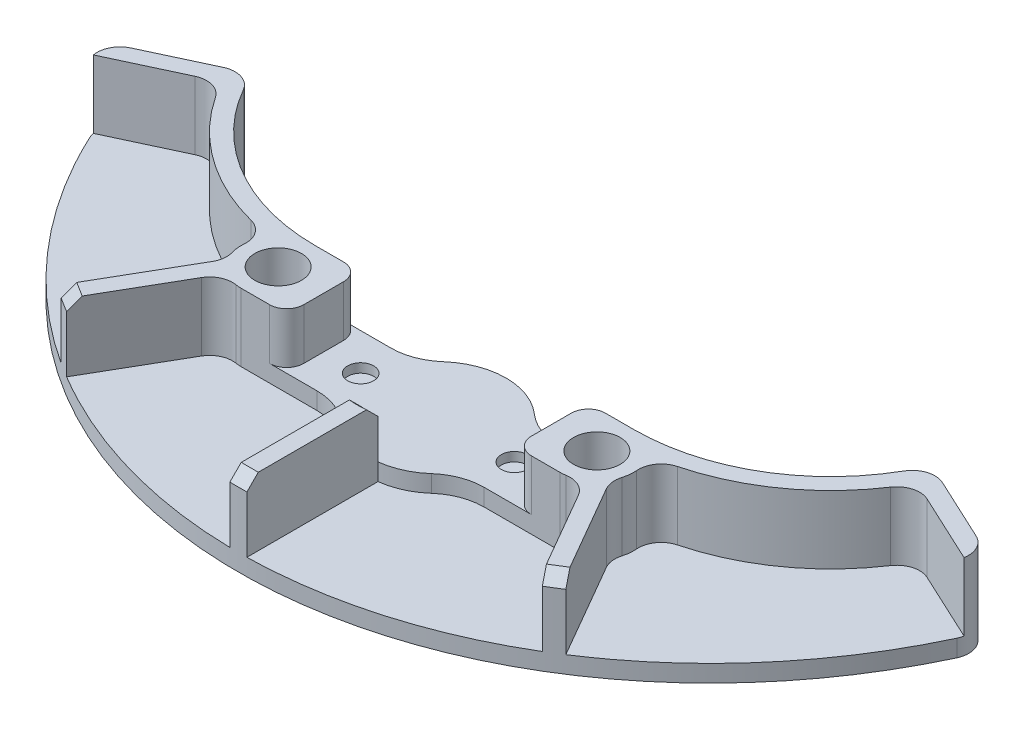
SolidWorks part; units mm, degrees
material "Custom Plastic"
ref_plane "Front Plane" through (0, 0, 0) normal (0, 0, 1) x (1, 0, 0)
ref_plane "Top Plane" through (0, 0, 0) normal (0, 1, 0) x (1, 0, 0)
ref_plane "Right Plane" through (0, 0, 0) normal (1, 0, 0) x (0, 0, -1)
sketch "Sketch1" plane through (0, 0, 0) normal (0, 1, 0) x (1, 0, 0)
  line L0 (-1000, 0) -> (49000, 0) construction
  line L1 (0, -1000) -> (0, 49000) construction
  line L2 (-7.3514, 3.25) -> (-14, 3.25)
  line L3 (-7.3514, -3.25) -> (-14, -3.25)
  line L4 (7.3514, -3.25) -> (14, -3.25)
  line L5 (7.3514, 3.25) -> (14, 3.25)
  circle A1 centre (-6.75, 0) radius 1.14
  arc A5 (3.99, 4.5211) -> (-3.99, 4.5211) centre (0, 0) ccw
  arc A6 (-7.3514, 3.25) -> (-3.99, 4.5211) centre (-7.3514, 8.33) ccw
  circle A17 centre (-14, 0) radius 2.05
  arc A18 (-14, 3.25) -> (-14, -3.25) centre (-14, 0) ccw
  arc A19 (3.99, -4.5211) -> (-3.99, -4.5211) centre (0, 0) cw
  arc A20 (-7.3514, -3.25) -> (-3.99, -4.5211) centre (-7.3514, -8.33) cw
  arc A21 (7.3514, 3.25) -> (3.99, 4.5211) centre (7.3514, 8.33) cw
  arc A22 (7.3514, -3.25) -> (3.99, -4.5211) centre (7.3514, -8.33) ccw
  circle A23 centre (6.75, 0) radius 1.14
  circle A24 centre (14, 0) radius 2.05
  arc A25 (14, 3.25) -> (14, -3.25) centre (14, 0) cw
  dimension "D1" = 6.03
  dimension "D3" = 2.28
  dimension "D4" = 5.08
  dimension "D6" = 4.1
  dimension "D8" = 6.5
  dimension "D2" = 13.5
  dimension "D7" = 28
extrude "Boss-Extrude2" add sketch "Sketch1" along normal blind 1.5
sketch "Sketch2" plane through (0, 1.5, 0) normal (0, 1, 0) x (1, 0, 0)
  line L0 (0, -1000) -> (0, 49000) construction
  line L1 (-14, 3.25) -> (-10, 3.25)
  line L2 (-7.3514, 3.25) -> (-14, 3.25) construction
  line L3 (-10, 3.25) -> (-10, -3.25)
  line L4 (-14, -3.25) -> (-7.3514, -3.25) construction
  line L5 (-10, -3.25) -> (-14, -3.25)
  line L6 (10, -3.25) -> (14, -3.25)
  line L7 (10, 3.25) -> (10, -3.25)
  line L8 (14, 3.25) -> (10, 3.25)
  arc A0 (-14, 3.25) -> (-14, -3.25) centre (-14, 0) ccw
  circle A2 centre (-14, 0) radius 2.05 construction
  circle A3 centre (-14, 0) radius 2.05
  circle A4 centre (14, 0) radius 2.05
  arc A5 (14, 3.25) -> (14, -3.25) centre (14, 0) cw
  dimension "D1" = 4
extrude "Boss-Extrude3" add sketch "Sketch2" along normal blind 4.47
fillet "Fillet1" radius 1.5 4 edges at (10, 3.735, 3.25) (10, 3.735, -3.25) (-10, 3.735, 3.25) (-10, 3.735, -3.25)
sketch "Sketch3" plane through (0, 0, 0) normal (0, -1, 0) x (1, 0, 0)
  line L0 (0, -1000) -> (0, 49000) construction
  line L1 (-1000, -27.5) -> (49000, -27.5) construction
  line L2 (0, -27.5) -> (-45315.3894, 21103.4131) construction
  line L3 (0, -27.5) -> (-16.815, 1.6244) construction
  line L4 (0, -27.5) -> (45315.3894, 21103.4131) construction
  line L5 (0, -27.5) -> (16.815, 1.6244) construction
  line L6 (-38.8951, -9.3629) -> (-29.832, -13.5891)
  line L7 (-22.1669, 10.8942) -> (-17.3063, 2.4755)
  line L8 (22.1669, 10.8942) -> (17.3063, 2.4755)
  line L9 (38.8951, -9.3629) -> (29.832, -13.5891)
  line L10 (14, -3.25) -> (7.3514, -3.25) construction
  line L11 (-7.3514, -3.25) -> (-14, -3.25) construction
  line L12 (14, -3.25) -> (7.3514, -3.25)
  line L13 (-7.3514, -3.25) -> (-14, -3.25)
  line L14 (17.3063, 2.4755) -> (25000, 43273.7702) construction
  line L15 (-17.3063, 2.4755) -> (-25000, 43273.7702) construction
  arc A0 (-14, 3.25) -> (-14, -3.25) centre (-14, 0) ccw construction
  arc A1 (-16.815, 1.6244) -> (-14, -3.25) centre (-14, 0) ccw
  arc A2 (-17.119, 0.9134) -> (-17.3063, 2.4755) centre (-19.0384, 1.4755) ccw
  arc A3 (16.815, 1.6244) -> (14, -3.25) centre (14, 0) cw
  arc A4 (17.119, 0.9134) -> (17.3063, 2.4755) centre (19.0384, 1.4755) cw
  arc A5 (-14, -3.25) -> (-29.832, -13.5891) centre (-14, -20.5412) ccw
  arc A6 (14, -3.25) -> (29.832, -13.5891) centre (14, -20.5412) cw
  arc A7 (7.3514, -3.25) -> (3.99, -4.5211) centre (7.3514, -8.33) ccw construction
  arc A8 (-3.99, -4.5211) -> (3.99, -4.5211) centre (0, 0) ccw construction
  arc A9 (-3.99, -4.5211) -> (-7.3514, -3.25) centre (-7.3514, -8.33) ccw construction
  arc A10 (7.3514, -3.25) -> (3.99, -4.5211) centre (7.3514, -8.33) ccw
  arc A11 (-3.99, -4.5211) -> (3.99, -4.5211) centre (0, 0) ccw
  arc A12 (-3.99, -4.5211) -> (-7.3514, -3.25) centre (-7.3514, -8.33) ccw
  ellipse E0 centre (0, -27.5) end of major axis (0, 17.5) minor radius 42.5 (38.8951, -9.3629) -> (-38.8951, -9.3629) ccw
  point P5 (-22.1669, 10.8942)
  point P46 (0, 0)
  arc M1 (-14, 3.25) -> (-14, -3.25) centre (-14, 0) ccw
  line M2 (-14, -3.25) -> (-7.3514, -3.25)
  arc M3 (-7.3514, -3.25) -> (-3.99, -4.5211) centre (-7.3514, -8.33) cw
  arc M4 (-3.99, -4.5211) -> (3.99, -4.5211) centre (0, 0) ccw
  arc M5 (3.99, -4.5211) -> (7.3514, -3.25) centre (7.3514, -8.33) cw
  line M6 (7.3514, -3.25) -> (14, -3.25)
  arc M7 (14, -3.25) -> (14, 3.25) centre (14, 0) ccw
  line M8 (14, 3.25) -> (7.3514, 3.25)
  arc M9 (7.3514, 3.25) -> (3.99, 4.5211) centre (7.3514, 8.33) cw
  arc M10 (3.99, 4.5211) -> (-3.99, 4.5211) centre (0, 0) ccw
  arc M11 (-3.99, 4.5211) -> (-7.3514, 3.25) centre (-7.3514, 8.33) cw
  line M12 (-7.3514, 3.25) -> (-14, 3.25)
  circle M13 centre (-14, 0) radius 2.05
  circle M14 centre (-6.75, 0) radius 1.14
  circle M15 centre (6.75, 0) radius 1.14
  circle M16 centre (14, 0) radius 2.05
  dimension "D1" = 85
  dimension "D7" = 2
  dimension "D2" = 45
  dimension "D3" = 27.5
  dimension "D4" = 30
  dimension "D5" = 35
  dimension "D6" = 10
extrude "Boss-Extrude4" add sketch "Sketch3" along normal blind 1.5 contours L7 E0 L6 A5 A1 A2 | L8 E0 L7 A2 A3 A4 M1 M12 M11 M10 M9 M8 M7 | L9 E0 L8 A4 A6 M7 | A1 A3 M12 M1 M2 M3 M4 M5 M6 M7 M8 M9 M10 M11 M13 M15 M16 M14 region at (-27.0965, 0, -1.8047) region at (0, 0, 9.8793) region at (0, 0, 0) region at (27.0965, 0, -1.8047)
sketch "Sketch4" plane through (0, 0, 0) normal (0, 1, 0) x (1, 0, 0)
  line L0 (-38.8951, 9.3629) -> (-29.832, 13.5891) construction
  line L1 (-38.8951, 9.3629) -> (-29.832, 13.5891)
  line L2 (-38.2612, 8.0034) -> (-32.1622, 10.8474)
  line L3 (38.8951, 9.3629) -> (29.832, 13.5891) construction
  line L4 (38.8951, 9.3629) -> (29.832, 13.5891)
  line L5 (32.1622, 10.8474) -> (38.2965, 7.987)
  line L6 (-22.1669, -10.8942) -> (-17.3063, -2.4755) construction
  line L7 (-22.1669, -10.8942) -> (-17.3063, -2.4755)
  line L8 (-20.8679, -11.6442) -> (-16.5608, -4.1842)
  line L9 (22.1669, -10.8942) -> (17.3063, -2.4755) construction
  line L10 (7.3514, -3.25) -> (14, -3.25) construction
  line L11 (-20.8679, -11.6442) -> (-16.0073, -3.2255) construction
  line L12 (0.75, -17.493) -> (0.75, -6.03)
  line L13 (-0.75, -17.493) -> (-0.75, -6.03)
  line L14 (22.1669, -10.8942) -> (17.3063, -2.4755)
  line L15 (20.8927, -11.6872) -> (16.5608, -4.1842)
  line L16 (20.8679, -11.6442) -> (16.0073, -3.2255) construction
  line L17 (0, -1000) -> (0, 49000) construction
  line L18 (0, -17.5) -> (0, -6.03) construction
  line L19 (-14, -3.25) -> (-7.3514, -3.25) construction
  line L20 (7.3514, -3.25) -> (14, -3.25)
  line L21 (-14, -3.25) -> (-7.3514, -3.25)
  line L22 (-20.8679, -11.6442) -> (-20.8927, -11.6872)
  line L26 (-38.2612, 8.0034) -> (-38.2965, 7.987)
  line L27 (-0.75, -6.03) -> (-0.75, -5.9832)
  line L28 (0.75, -6.03) -> (0.75, -5.9832)
  line L29 (-0.75, -17.5) -> (-0.75, -6.03) construction
  line L30 (0.75, -17.5) -> (0.75, -6.03) construction
  line L32 (-38.2612, 8.0034) -> (-29.1981, 12.2296) construction
  arc A0 (17.119, -0.9134) -> (17.3063, -2.4755) centre (19.0384, -1.4755) ccw construction
  arc A1 (17.119, -0.9134) -> (17.3063, -2.4755) centre (19.0384, -1.4755) ccw
  arc A2 (14, -3.25) -> (14, 3.25) centre (14, 0) ccw construction
  arc A3 (14, -3.25) -> (17.119, -0.9134) centre (14, 0) ccw
  arc A4 (-17.3063, -2.4755) -> (-17.119, -0.9134) centre (-19.0384, -1.4755) ccw construction
  arc A5 (-17.3063, -2.4755) -> (-17.119, -0.9134) centre (-19.0384, -1.4755) ccw
  arc A6 (-14, 3.25) -> (-14, -3.25) centre (-14, 0) ccw construction
  arc A7 (-17.119, -0.9134) -> (-14, -3.25) centre (-14, 0) ccw
  arc A8 (-14.513, -3.2092) -> (-16.5608, -4.1842) centre (-14.8288, -5.1842) ccw
  arc A9 (16.5608, -4.1842) -> (14.513, -3.2092) centre (14.8288, -5.1842) ccw
  arc A10 (14, 3.25) -> (29.832, 13.5891) centre (14, 20.5412) ccw construction
  arc A11 (14, 3.25) -> (29.832, 13.5891) centre (14, 20.5412) ccw
  arc A12 (-29.832, 13.5891) -> (-14, 3.25) centre (-14, 20.5412) ccw construction
  arc A13 (-29.832, 13.5891) -> (-14, 3.25) centre (-14, 20.5412) ccw
  arc A14 (-14, 3.25) -> (-16.815, -1.6244) centre (-14, 0) ccw construction
  arc A15 (-14, 3.25) -> (-16.815, -1.6244) centre (-14, 0) ccw
  arc A16 (16.815, -1.6244) -> (14, 3.25) centre (14, 0) ccw construction
  arc A17 (16.815, -1.6244) -> (14, 3.25) centre (14, 0) ccw
  arc A18 (-3.99, -4.5211) -> (3.99, -4.5211) centre (0, 0) ccw construction
  arc A19 (-3.99, -4.5211) -> (3.99, -4.5211) centre (0, 0) ccw
  arc A20 (7.3514, -3.25) -> (3.99, -4.5211) centre (7.3514, -8.33) ccw construction
  arc A21 (-3.99, -4.5211) -> (-7.3514, -3.25) centre (-7.3514, -8.33) ccw construction
  arc A22 (7.3514, -3.25) -> (3.99, -4.5211) centre (7.3514, -8.33) ccw
  arc A23 (-3.99, -4.5211) -> (-7.3514, -3.25) centre (-7.3514, -8.33) ccw
  arc A25 (-29.6512, 10.1417) -> (-18.7298, 2.355) centre (-14, 20.5412) ccw
  arc A26 (-29.6512, 10.1417) -> (-32.1622, 10.8474) centre (-31.317, 9.0348) ccw
  arc A27 (-17.2396, 0.2596) -> (-18.7298, 2.355) centre (-19.2332, 0.4194) ccw
  arc A28 (29.6512, 10.1417) -> (32.1622, 10.8474) centre (31.317, 9.0348) cw
  arc A29 (17.2396, 0.2596) -> (18.7298, 2.355) centre (19.2332, 0.4194) cw
  arc A30 (29.6512, 10.1417) -> (18.7298, 2.355) centre (14, 20.5412) cw
  ellipse E0 centre (0, 27.5) end of major axis (0, 72.5) minor radius 42.5 (-38.8951, 9.3629) -> (38.8951, 9.3629) ccw construction
  ellipse E1 centre (0, 27.5) end of major axis (0, 72.5) minor radius 42.5 (-38.8951, 9.3629) -> (38.8951, 9.3629) ccw
  point P20 (38.1537, 8.0536)
  arc M11 (-14, -3.25) -> (-14, 3.25) centre (-14, 0) cw
  arc M12 (-14, 3.25) -> (-29.832, 13.5891) centre (-14, 20.5412) cw
  line M13 (-29.832, 13.5891) -> (-38.8951, 9.3629)
  ellipse M14 centre (0, 27.5) end of major axis (0, -17.5) minor radius 42.5 (-38.8951, 9.3629) -> (38.8951, 9.3629) ccw
  line M15 (38.8951, 9.3629) -> (29.832, 13.5891)
  arc M16 (29.832, 13.5891) -> (14, 3.25) centre (14, 20.5412) cw
  arc M17 (14, 3.25) -> (14, -3.25) centre (14, 0) cw
  arc M20 (3.99, -4.5211) -> (-3.99, -4.5211) centre (0, 0) cw
  dimension "D4" = 2
  dimension "D6" = 2
  dimension "D9" = 1.5
  dimension "D10" = 2
  dimension "D11" = 2
  dimension "D1" = 1.5
  dimension "D3" = 1.5
  dimension "D5" = 1.5
  dimension "D7" = 0.75
  dimension "D8" = 0.75
extrude "Boss-Extrude5" add sketch "Sketch4" along normal up to surface (5.97 mm away) contours L26 L2 M12 M13 M14 | A8 A7 A5 L7 L22 L8 M11 M14 | L12 L28 L27 L13 M20 M14 | A9 L15 L14 A1 A3 M14 M17 | M14 M15 M16 region at (-27.2427, 0, -7.7332) region at (-18.8155, 0, 6.6268) region at (0, 0, 11.756) region at (18.8155, 0, 6.6268) region at (27.2427, 0, -7.7332) up to face at (12.2714, 5.97, 0)
fillet "Fillet3" radius 2 4 edges at (38.8951, 2.235, -9.3629) (29.832, 2.235, -13.5891) (-29.832, 2.235, -13.5891) (-38.8951, 2.235, -9.3629)
chamfer "Chamfer3" distance 1 angle 45 4 edges at (21.5331, 5.97, 11.2966) (0, 5.97, 6.03) (0, 5.97, 17.5) (-21.5331, 5.97, 11.2966)
chamfer "Chamfer4" distance 0.5 angle 45 2 edges at (-14, -1.5, -2.05) (14, -1.5, -2.05)
sketch "Sketch8" plane through (0, -1.5, 0) normal (0, -1, 0) x (1, 0, 0)
  line L0 (0, -1000) -> (0, 49000) construction
  circle A0 centre (-6.75, 0) radius 2.75
  circle A1 centre (-6.75, 0) radius 1.14 construction
  circle A2 centre (6.75, 0) radius 2.75
  dimension "D1" = 5.5
extrude "Cut-Extrude1" cut sketch "Sketch8" against normal blind 2
sketch "Sketch9" plane through (0, 0.5, 0) normal (0, -1, 0) x (1, 0, 0)
  circle A0 centre (-6.75, 0) radius 1.14 construction
  circle A1 centre (-6.75, 0) radius 1.14
  circle A2 centre (6.75, 0) radius 1.14 construction
  circle A3 centre (6.75, 0) radius 1.14
extrude "Boss-Extrude6" add sketch "Sketch9" against normal blind 0.2
